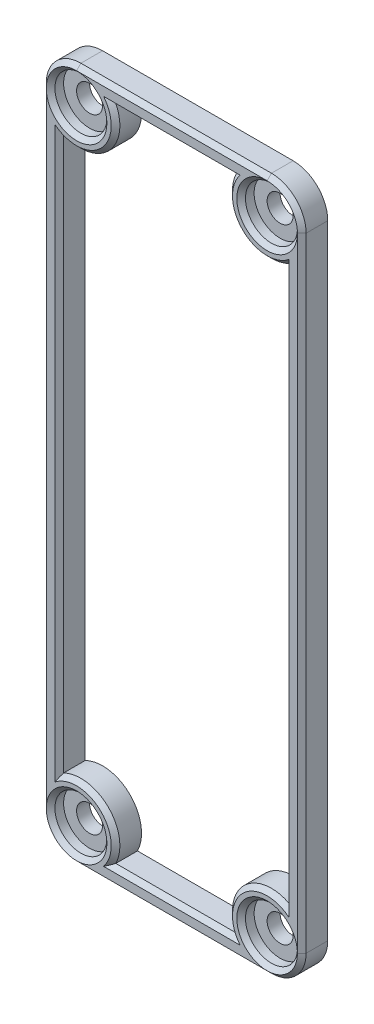
SolidWorks part; units mm, degrees
ref_plane "Front Plane" through (0, 0, 0) normal (0, 0, 1) x (1, 0, 0)
ref_plane "Top Plane" through (0, 0, 0) normal (0, 1, 0) x (1, 0, 0)
ref_plane "Right Plane" through (0, 0, 0) normal (1, 0, 0) x (0, 0, -1)
sketch "Sketch1" plane through (0, 0, 0) normal (0, 0, 1) x (1, 0, 0)
  line L1 (11, -40) -> (-11, -40)
  line L2 (15, -36) -> (15, 36)
  line L3 (11, 40) -> (-11, 40)
  line L4 (-15, -36) -> (-15, 36)
  line L5 (15, -40) -> (-15, 40) construction
  line L6 (15, 40) -> (-15, -40) construction
  arc A0 (11, -40) -> (15, -36) centre (11, -36) ccw
  arc A1 (-11, -40) -> (-15, -36) centre (-11, -36) cw
  arc A2 (15, 36) -> (11, 40) centre (11, 36) ccw
  arc A3 (-11, 40) -> (-15, 36) centre (-11, 36) ccw
  point P0 (0, 0)
  dimension "D3" = 4
  dimension "D1" = 30
  dimension "D2" = 80
extrude "Base" add sketch "Sketch1" along normal blind 3
sketch "Sketch2" plane through (0, 0, 3) normal (0, 0, 1) x (1, 0, 0)
  line L1 (11, -36) -> (-11, -36) construction
  line L2 (11, -36) -> (11, 36) construction
  line L3 (11, 36) -> (-11, 36) construction
  line L4 (-11, -36) -> (-11, 36) construction
  line L5 (11, -36) -> (-11, 36) construction
  line L6 (11, 36) -> (-11, -36) construction
  circle A0 centre (-11, 36) radius 1.5
  circle A1 centre (-11, -36) radius 1.5
  circle A2 centre (11, -36) radius 1.5
  circle A3 centre (11, 36) radius 1.5
  point P0 (0, 0)
  dimension "D1" = 3
  dimension "D2" = 22
  dimension "D3" = 72
extrude "Cut-Extrude1" cut sketch "Sketch2" against normal through all
sketch "Sketch3" plane through (0, 0, 3) normal (0, 0, 1) x (1, 0, 0)
  line L14 (13, -31.9689) -> (13, 31.9689)
  line L16 (-13, 36) -> (-13, -36)
  line L17 (-13, 31.9689) -> (-13, -31.9689)
  line L19 (11, 38) -> (-11, 38)
  line L20 (6.9689, 38) -> (-6.9689, 38)
  line L22 (-11, -38) -> (11, -38)
  line L23 (-6.9689, -38) -> (6.9689, -38)
  arc A0 (-13, 31.9689) -> (-6.9689, 38) centre (-11, 36) ccw
  arc A1 (6.9689, 38) -> (13, 31.9689) centre (11, 36) ccw
  arc A2 (-6.9689, -38) -> (-13, -31.9689) centre (-11, -36) ccw
  arc A3 (13, -31.9689) -> (6.9689, -38) centre (11, -36) ccw
  circle A19 centre (11, 36) radius 1.5 construction
  circle A20 centre (-11, -36) radius 1.5 construction
  circle A30 centre (11, -36) radius 1.5 construction
  circle A31 centre (-11, 36) radius 1.5 construction
  dimension "D4" = 2
  dimension "D15" = 4.5
  dimension "D5" = 2
  dimension "D6" = 2
extrude "Cut-Extrude2" cut sketch "Sketch3" against normal through all contours L17 | L17 A2 | A2 L23 A3 | A3 L14 | L14 | L14 | L14 A1 | A1 L20 A0 | L17 | A0 L17 region at (0, 0, 3)
sketch "Sketch6" plane through (0, 0, 3) normal (0, 0, 1) x (1, 0, 0)
  circle A0 centre (-11, -36) radius 3
  circle A1 centre (11, -36) radius 3
  circle A2 centre (11, 36) radius 3
  circle A3 centre (-11, 36) radius 3
  dimension "D1" = 6
extrude "Cut-Extrude3" cut sketch "Sketch6" against normal blind 1.5
chamfer "Chamfer2" distance 0.5 angle 45 20 edges at (7.818, -32.818, 3) (-7.818, -32.818, 3) (-7.818, 32.818, 3) (7.818, 32.818, 3) (0, -40, 3) (-13.8284, -38.8284, 3) (-15, 0, 3) (-13.8284, 38.8284, 3) (0, 40, 3) (13.8284, 38.8284, 3) (15, 0, 3) (13.8284, -38.8284, 3) (-8, -36, 3) (-8, 36, 3) (14, 36, 3) (14, -36, 3) (13, 0, 3) (0, -38, 3) (0, 38, 3) (-13, 0, 3)
equation "\"D3@Sketch2\"=\"D2@Sketch1\"-8"
